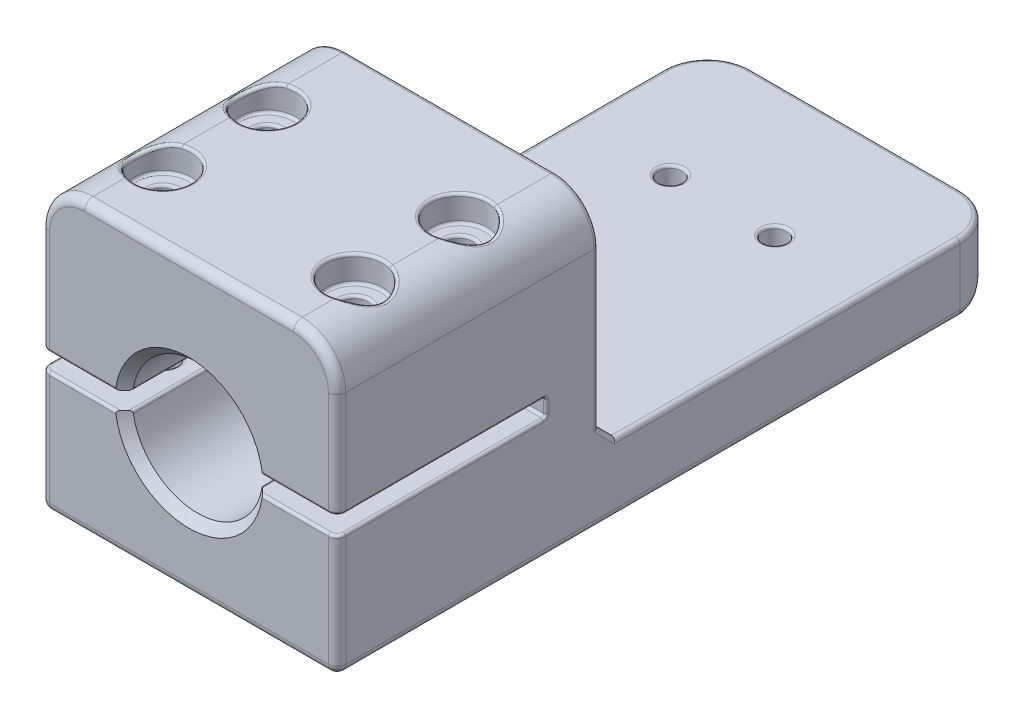
SolidWorks part; units mm, degrees
ref_plane "정면" through (0, 0, 0) normal (0, 0, 1) x (1, 0, 0)
ref_plane "윗면" through (0, 0, 0) normal (0, 1, 0) x (1, 0, 0)
ref_plane "우측면" through (0, 0, 0) normal (1, 0, 0) x (0, 0, -1)
sketch "스케치1" plane through (0, 0, 0) normal (0, 0, 1) x (1, 0, 0)
  line L1 (-17, 12.5) -> (17, 12.5)
  line L2 (-17, 12.5) -> (-17, -12.5)
  line L3 (-17, -12.5) -> (17, -12.5)
  line L4 (17, 12.5) -> (17, -12.5)
  line L5 (-17, 12.5) -> (17, -12.5) construction
  line L6 (-17, -12.5) -> (17, 12.5) construction
  point P0 (0, 0)
  dimension "D1" = 34
  dimension "D2" = 25
extrude "보스-돌출1" add sketch "스케치1" along normal blind 22
sketch "스케치4" plane through (0, 0, 0) normal (0, 0, -1) x (-1, 0, 0)
  line L4 (-17, 12.5) -> (-17, -12.5)
  line L5 (-17, -12.5) -> (17, -12.5)
  line L6 (17, -12.5) -> (17, 12.5)
  line L7 (17, 12.5) -> (-17, 12.5)
  line L8 (-17, 12.5) -> (-17, -12.5)
  line L9 (-17, -12.5) -> (17, -12.5)
  line L10 (17, -12.5) -> (17, 12.5)
  line L11 (17, 12.5) -> (-17, 12.5)
  dimension "D1" = 0
extrude "보스-돌출2" add sketch "스케치4" along normal blind 8
sketch "스케치5" plane through (0, -12.5, 0) normal (0, -1, 0) x (1, 0, 0)
  line L0 (17, 22) -> (17, -8) construction
  line L1 (-17, -8) -> (17, -8)
  line L2 (-17, -8) -> (-17, -54.5)
  line L3 (-17, -54.5) -> (17, -54.5)
  line L4 (17, -8) -> (17, -54.5)
  dimension "D1" = 46.5
extrude "보스-돌출3" add sketch "스케치5" against normal blind 8
sketch "스케치6" plane through (0, 12.5, 0) normal (0, 1, 0) x (1, 0, 0)
  line L4 (17, -22) -> (17, 8)
  line L5 (17, 8) -> (-17, 8)
  line L6 (-17, 8) -> (-17, -22)
  line L7 (-17, -22) -> (17, -22)
  line L8 (17, -22) -> (17, 8)
  line L9 (17, 8) -> (-17, 8)
  line L10 (-17, 8) -> (-17, -22)
  line L11 (-17, -22) -> (17, -22)
  dimension "D1" = 0
sketch "스케치7" plane through (0, 12.5, 0) normal (0, 1, 0) x (1, 0, 0)
  line L4 (17, -22) -> (17, 8)
  line L5 (17, 8) -> (-17, 8)
  line L6 (-17, 8) -> (-17, -22)
  line L7 (-17, -22) -> (17, -22)
  line L8 (17, -22) -> (17, 8)
  line L9 (17, 8) -> (-17, 8)
  line L10 (-17, 8) -> (-17, -22)
  line L11 (-17, -22) -> (17, -22)
  dimension "D1" = 0
extrude "보스-돌출5" add sketch "스케치7" along normal blind 8
sketch "스케치8" plane through (0, 0, 22) normal (0, 0, 1) x (1, 0, 0)
  circle A0 centre (0, 2.5) radius 7.5
  dimension "D1" = 15
  dimension "D2" = 2.5
extrude "컷-돌출1" cut sketch "스케치8" against normal blind 24
sketch "스케치9" plane through (0, 0, 22) normal (0, 0, 1) x (1, 0, 0)
  line L0 (17, -12.5) -> (17, 20.5) construction
  line L1 (-17, 3.5) -> (17, 3.5)
  line L2 (-17, 3.5) -> (-17, 1.5)
  line L3 (-17, 1.5) -> (17, 1.5)
  line L4 (17, 3.5) -> (17, 1.5)
  line L5 (-17, 3.5) -> (17, 1.5) construction
  line L6 (-17, 1.5) -> (17, 3.5) construction
  circle A0 centre (0, 2.5) radius 7.5 construction
  circle A1 centre (0, 2.5) radius 7.5 construction
  dimension "D1" = 2
extrude "컷-돌출2" cut sketch "스케치9" against normal blind 24
hole_wizard "M3 소켓 머리 캡 나사용 카운터보어1" positions "스케치10" profile "스케치11" counterbore size "M3" standard "KS" end condition through all
sketch "스케치10" plane through (0, 20.5, 0) normal (0, 1, 0) x (1, 0, 0)
  line L0 (17, -22) -> (17, 8) construction
  line L1 (-17, -22) -> (17, -22) construction
  line L2 (-17, 8) -> (-17, -22) construction
  point P0 (11, -2)
  point P2 (-11, -2)
  dimension "D1" = 6
  dimension "D2" = 20
  dimension "D3" = 6
  dimension "D4" = 20
sketch "스케치11" plane through (11, 20.5, 2) normal (1, 0, 0) x (0, 0, 1)
  line L0 (0, 0) -> (0, 33)
  line L1 (0, 33) -> (1.6, 33)
  line L3 (1.6, 33) -> (1.6, 3)
  line L4 (1.6, 3) -> (3.25, 3)
  line L5 (3.25, 3) -> (3.25, 0)
  line L7 (3.25, 0) -> (0, 0)
  line L11 (0, -6.35) -> (0, 107.95) construction
  dimension "관통 구멍 지름" = 3.2
  dimension "관통 구멍 깊이" = 33
  dimension "카운터보어 지름" = 6.5
  dimension "카운터보어 깊이" = 3
hole_wizard "M3 소켓 머리 캡 나사용 카운터보어2" positions "스케치16" profile "스케치17" counterbore size "M3" standard "KS" end condition through all
sketch "스케치16" plane through (0, 20.5, 0) normal (0, 1, 0) x (1, 0, 0)
  line L0 (17, -22) -> (17, 8) construction
  line L1 (-17, 8) -> (-17, -22) construction
  line L2 (-17, -22) -> (17, -22) construction
  point P0 (-11, -14)
  point P2 (11, -14)
  dimension "D1" = 6
  dimension "D2" = 6
  dimension "D3" = 8
  dimension "D4" = 8
sketch "스케치17" plane through (-11, 20.5, 14) normal (1, 0, 0) x (0, 0, 1)
  line L0 (0, 0) -> (0, 33)
  line L1 (0, 33) -> (1.6, 33)
  line L3 (1.6, 33) -> (1.6, 3)
  line L4 (1.6, 3) -> (3.25, 3)
  line L5 (3.25, 3) -> (3.25, 0)
  line L7 (3.25, 0) -> (0, 0)
  line L11 (0, -6.35) -> (0, 107.95) construction
  dimension "관통 구멍 지름" = 3.2
  dimension "관통 구멍 깊이" = 33
  dimension "카운터보어 지름" = 6.5
  dimension "카운터보어 깊이" = 3
sketch "스케치12" plane through (0, -12.5, 0) normal (0, -1, 0) x (1, 0, 0)
  line L1 (-13.725, 4.725) -> (-8.275, 4.725)
  line L2 (-13.725, 4.725) -> (-13.725, -0.725)
  line L3 (-13.725, -0.725) -> (-8.275, -0.725)
  line L4 (-8.275, 4.725) -> (-8.275, -0.725)
  line L5 (-13.725, 4.725) -> (-8.275, -0.725) construction
  line L6 (-13.725, -0.725) -> (-8.275, 4.725) construction
  line L7 (8.275, 4.725) -> (13.725, 4.725)
  line L8 (8.275, 4.725) -> (8.275, -0.725)
  line L9 (8.275, -0.725) -> (13.725, -0.725)
  line L10 (13.725, 4.725) -> (13.725, -0.725)
  line L11 (8.275, 4.725) -> (13.725, -0.725) construction
  line L12 (8.275, -0.725) -> (13.725, 4.725) construction
  line L13 (-13.725, 16.725) -> (-8.275, 16.725)
  line L14 (-13.725, 16.725) -> (-13.725, 11.275)
  line L15 (-13.725, 11.275) -> (-8.275, 11.275)
  line L16 (-8.275, 16.725) -> (-8.275, 11.275)
  line L17 (-13.725, 16.725) -> (-8.275, 11.275) construction
  line L18 (-13.725, 11.275) -> (-8.275, 16.725) construction
  line L19 (8.275, 16.725) -> (13.725, 16.725)
  line L20 (8.275, 16.725) -> (8.275, 11.275)
  line L21 (8.275, 11.275) -> (13.725, 11.275)
  line L22 (13.725, 16.725) -> (13.725, 11.275)
  line L23 (8.275, 16.725) -> (13.725, 11.275) construction
  line L24 (8.275, 11.275) -> (13.725, 16.725) construction
  point P0 (-11, 2)
  point P5 (11, 2)
  point P11 (-11, 14)
  point P17 (11, 14)
  dimension "D1" = 5.45
  dimension "D2" = 5.45
  dimension "D3" = 5.45
  dimension "D4" = 5.45
  dimension "D5" = 5.45
  dimension "D6" = 5.45
  dimension "D7" = 5.45
  dimension "D8" = 5.45
extrude "컷-돌출3" cut sketch "스케치12" against normal blind 2.45
chamfer "모따기1" distance 2 angle 45 1 edges at (0, -4.5, -8)
fillet "필렛1" radius 5 2 edges at (-17, 20.5, 7) (17, 20.5, 7)
chamfer "모따기2" distance 1 angle 45 2 edges at (0, -5, 22) (0, 10, 22)
fillet "필렛3" radius 1 10 edges at (17, 9.5, 22) (15.5355, 19.0355, 22) (0, 20.5, 22) (-15.5355, 19.0355, 22) (-17, 9.5, 22) (17, -5.5, 22) (-17, -5.5, 22) (0, -12.5, 22) (17, -12.5, -16.25) (-17, -12.5, -16.25)
fillet "필렛4" radius 5 5 edges at (-17, -8, -54.5) (-16.7071, -12.2071, -54.5) (0, -12.5, -54.5) (16.7071, -12.2071, -54.5) (17, -8, -54.5)
fillet "필렛5" radius 0.5 10 edges at (-17, 6.5, -8) (-15.5355, 19.0355, -8) (0, 20.5, -8) (15.5355, 19.0355, -8) (17, 6.5, -8) (-17, -4.5, -29.75) (-15.5355, -4.5, -53.0355) (0, -4.5, -54.5) (15.5355, -4.5, -53.0355) (17, -4.5, -29.75)
fillet "필렛6" radius 0.5 2 edges at (17, -3.5, -9) (-17, -3.5, -9)
hole_wizard "M2.5 소켓 머리 캡 나사용 카운터보어1" positions "스케치13" profile "스케치14" counterbore size "M2.5" standard "KS" end condition through all
sketch "스케치13" plane through (0, -12.5, 0) normal (0, -1, 0) x (-1, 0, 0)
  point P0 (-6, 15.25)
  point P3 (6, 15.25)
  point P6 (-6, 39.25)
  point P9 (6, 39.25)
sketch "스케치14" plane through (6, -12.5, -15.25) normal (1, 0, 0) x (0, 0, -1)
  line L0 (0, 0) -> (0, 33)
  line L1 (0, 33) -> (1.35, 33)
  line L3 (1.35, 33) -> (1.35, 2.5)
  line L4 (1.35, 2.5) -> (2.75, 2.5)
  line L5 (2.75, 2.5) -> (2.75, 0)
  line L7 (2.75, 0) -> (0, 0)
  line L11 (0, -6.35) -> (0, 107.95) construction
  dimension "관통 구멍 지름" = 2.7
  dimension "관통 구멍 깊이" = 33
  dimension "카운터보어 지름" = 5.5
  dimension "카운터보어 깊이" = 2.5
fillet "필렛7" radius 0.3 116 edges at (-12.2205, 1.5, 22) (-16.7071, 1.5, 21.7071) (12.2165, 3.5, -2) (0, -5, -2) (-17, 1.5, 9.5) (14.2455, 19.9674, 1.8283) (-14.2455, 19.9674, 2.1717) (17, 3.5, 9.5) (16.7071, 3.5, 21.7071) (17, 1.5, 9.5) (16.7071, 1.5, 21.7071) (-12.2205, 3.5, 22) (-16.7071, 3.5, 21.7071) (11, 17.5, 3.6) (11, 17.5, 5.25) (-11, 17.5, 3.6) (-11, 17.5, 5.25) (7.75, 20.5, 2) (-7.75, 20.5, 2) (7.433, 3.5, 9.5) (11, 3.5, 3.6) (12.2205, 3.5, 22) (11, 1.5, 0.4) (7.433, 1.5, 9.5) (12.2165, 1.5, -2) (12.2205, 1.5, 22) (17, 2.5, -2) (-11, 3.5, 3.6) (-7.433, 3.5, 9.5) (-12.2165, 3.5, -2) (-17, 3.5, 9.5) (0, 10, -2) (-7.433, 1.5, 9.5) (-11, 1.5, 0.4) (-12.2165, 1.5, -2) (-17, 2.5, -2) (6, -10, -18) (-6, -10, -18) (-6, -10, -16.6) (6, -10, -42) (6, -10, -40.6) (-6, -10, -42) (-6, -10, -40.6) (6, -10, -16.6) (6, -12.5, -18) (6, -4.5, -16.6) (-6, -4.5, -16.6) (6, -12.5, -42) (6, -4.5, -40.6) (-6, -12.5, -42) (-6, -4.5, -40.6) (-6, -12.5, -18) (13.725, -11.275, -0.725) (8.275, -11.275, -0.725) (8.275, -11.275, 4.725) (13.725, -11.275, 4.725) (11, -10.05, -0.725) (8.275, -10.05, 2) (11, -10.05, 4.725) (13.725, -10.05, 2) (-11, -10.05, 4.725) (-13.725, -10.05, 2) (-11, -10.05, -0.725) (-8.275, -11.275, 4.725) (-13.725, -11.275, 4.725) (-13.725, -11.275, -0.725) (-8.275, -11.275, -0.725) (-8.275, -10.05, 2) (11, -12.5, -0.725) (8.275, -12.5, 2) (11, -12.5, 4.725) (13.725, -12.5, 2) (-11, -12.5, 4.725) (-13.725, -12.5, 2) (-11, -12.5, -0.725) (11, -10.05, 0.4) (-11, -10.05, 0.4) (-8.275, -12.5, 2) (13.725, -11.275, 11.275) (8.275, -11.275, 11.275) (8.275, -11.275, 16.725) (13.725, -11.275, 16.725) (8.275, -10.05, 14) (-8.275, -11.275, 11.275) (-13.725, -11.275, 11.275) (-13.725, -11.275, 16.725) (-8.275, -11.275, 16.725) (13.725, -10.05, 14) (-11, -10.05, 11.275) (-8.275, -10.05, 14) (-11, -10.05, 16.725) (-13.725, -10.05, 14) (13.725, -12.5, 14) (-13.725, -12.5, 14) (-11, -12.5, 11.275) (-8.275, -12.5, 14) (-11, -12.5, 16.725) (8.275, -12.5, 14) (11, -12.5, 16.725) (11, -10.05, 16.725) (11, -10.05, 11.275) (11, -12.5, 11.275) (11, 17.5, 15.6) (11, 17.5, 17.25) (-11, 17.5, 15.6) (-11, 17.5, 17.25) (-11, -10.05, 12.4) (11, -10.05, 12.4) (-11, 3.5, 15.6) (-11, 1.5, 12.4) (7.75, 20.5, 14) (11, 1.5, 12.4) (11, 3.5, 15.6) (-14.2455, 19.9674, 14.1717) (14.2455, 19.9674, 13.8283) (-7.75, 20.5, 14)
